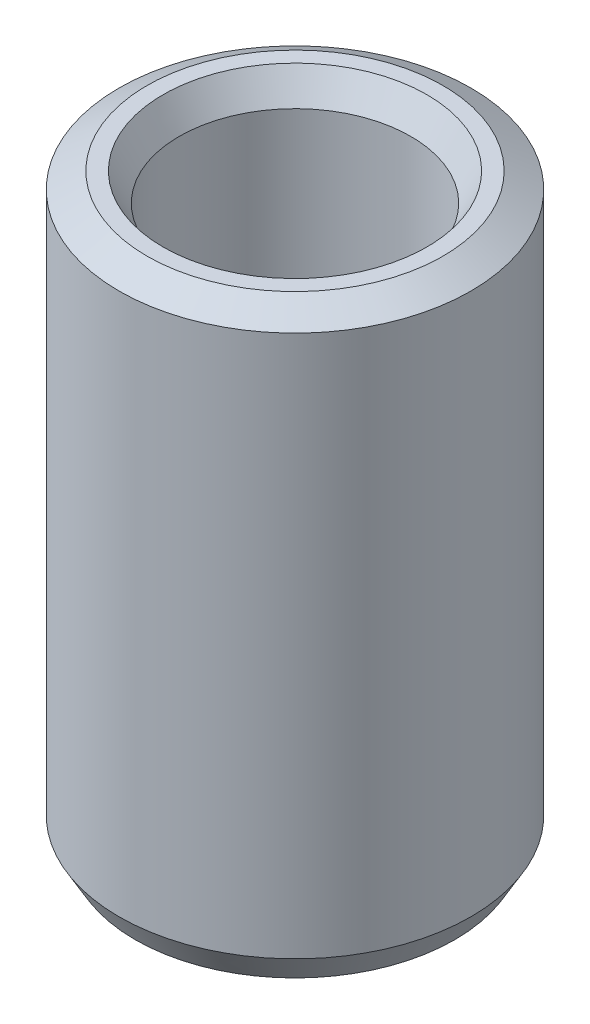
SolidWorks part; units mm, degrees
ref_plane "Front Plane" through (0, 0, 0) normal (0, 0, 1) x (1, 0, 0)
ref_plane "Top Plane" through (0, 0, 0) normal (0, 1, 0) x (1, 0, 0)
ref_plane "Right Plane" through (0, 0, 0) normal (1, 0, 0) x (0, 0, -1)
sketch "Sketch1" plane through (0, 0, 0) normal (0, 1, 0) x (1, 0, 0)
  circle A0 centre (0, 0) radius 12.5
  dimension "SLEEVE_OD" = 25
extrude "Boss-Extrude1" add sketch "Sketch1" along normal blind 41.6444
sketch "Sketch2" plane through (0, 0, 0) normal (0, 1, 0) x (1, 0, 0)
  circle A0 centre (0, 0) radius 8.2274
  dimension "BORE_D" = 16.4548
extrude "Cut-Extrude1" cut sketch "Sketch2" along normal through all
chamfer "Chamfer1" distance 1.1491 angle 60 4 edges at (0, 41.6444, 8.2274) (0, 0, 8.2274) (0, 0, 12.5) (0, 41.6444, 12.5) first distance on face at (0, 41.6444, 8.2274) first distance on face at (0, 0, 8.2274) first distance on face at (0, 41.6444, 12.5)
